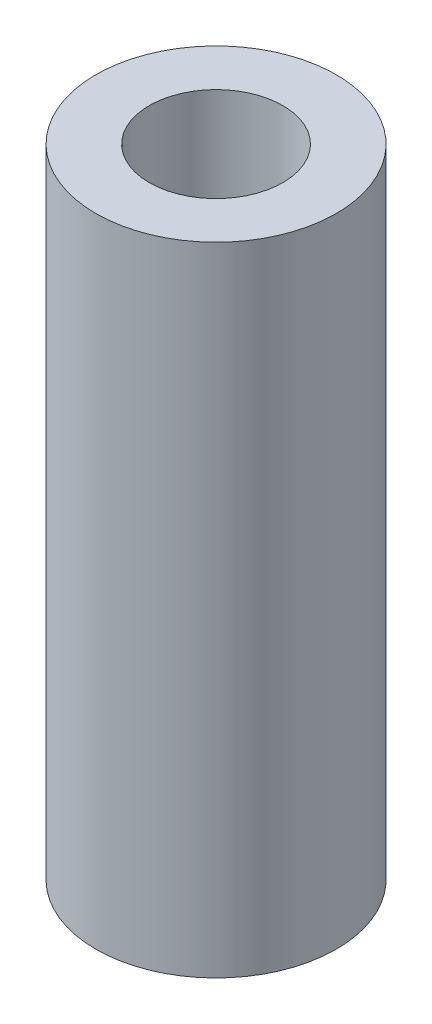
SolidWorks part; units mm, degrees
ref_plane "Front Plane" through (0, 0, 0) normal (0, 0, 1) x (1, 0, 0)
ref_plane "Top Plane" through (0, 0, 0) normal (0, 1, 0) x (1, 0, 0)
ref_plane "Right Plane" through (0, 0, 0) normal (1, 0, 0) x (0, 0, -1)
sketch "Sketch1" plane through (0, 0, 0) normal (0, 1, 0) x (1, 0, 0)
  circle A0 centre (0, 0) radius 2.5
  circle A1 centre (0, 0) radius 4.5
  dimension "D1" = 5
  dimension "D2" = 9
extrude "Boss-Extrude1" add sketch "Sketch1" along normal blind 23.85
